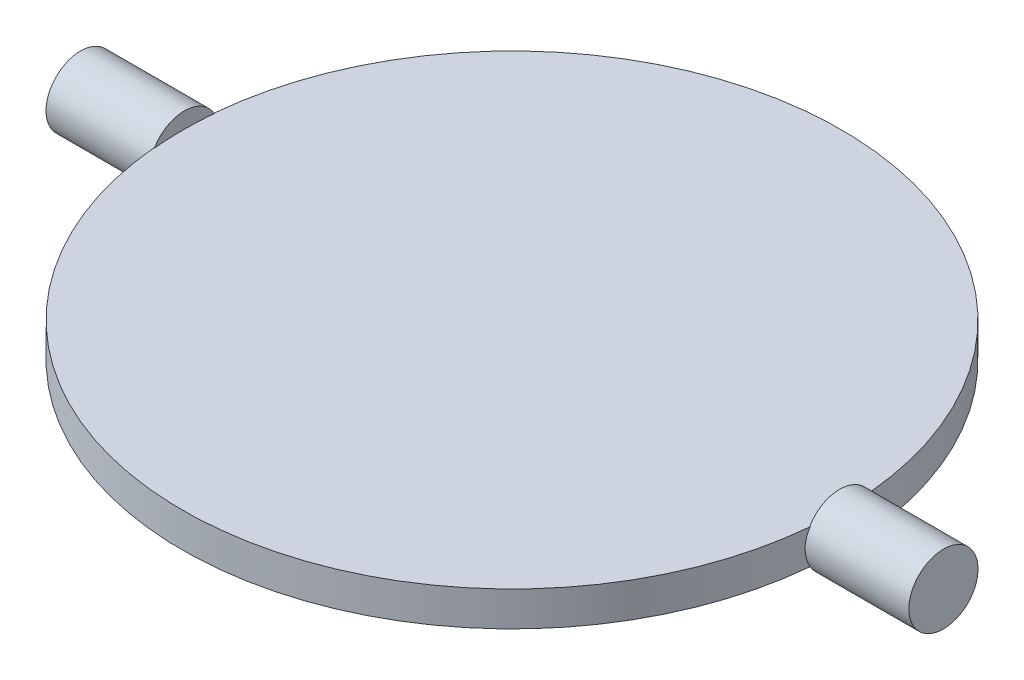
SolidWorks part; units mm, degrees
ref_plane "Front Plane" through (0, 0, 0) normal (0, 0, 1) x (1, 0, 0)
ref_plane "Top Plane" through (0, 0, 0) normal (0, 1, 0) x (1, 0, 0)
ref_plane "Right Plane" through (0, 0, 0) normal (1, 0, 0) x (0, 0, -1)
sketch "Sketch1" plane through (0, 0, 0) normal (0, 1, 0) x (1, 0, 0)
  line L0 (-76.4354, 0) -> (76.4354, 0) construction
  line L1 (-49.8894, 4) -> (-49.8894, -4)
  line L2 (0, 38.1) -> (0, -38.1) construction
  line L3 (-49.8894, 4) -> (-37.8894, 4)
  line L4 (-49.8894, -4) -> (-37.8894, -4)
  line L5 (49.8894, -4) -> (37.8894, -4)
  line L6 (49.8894, 4) -> (49.8894, -4)
  line L7 (49.8894, 4) -> (37.8894, 4)
  line L8 (-49.8894, 0) -> (-38.1, 0)
  line L9 (49.8894, 0) -> (38.1, 0)
  circle A0 centre (0, 0) radius 38.1
  point P6 (0, 0)
  point P9 (-49.8894, 0)
  dimension "D1" = 76.2
  dimension "D2" = 8
  dimension "D3" = 12
extrude "Boss-Extrude1" add sketch "Sketch1" along normal mid plane 4 contours A0 L1 region at (0, 0, 0)
revolve "Revolve1" add sketch "Sketch1<6>" angle 360 about L0 region at (-43.9595, 0, 2.0059) region at (43.9595, 0, 2.0059)
sketch "Sketch1<6>" plane through (0, 0, 0) normal (0, 1, 0) x (1, 0, 0) same geometry as "Sketch1"
